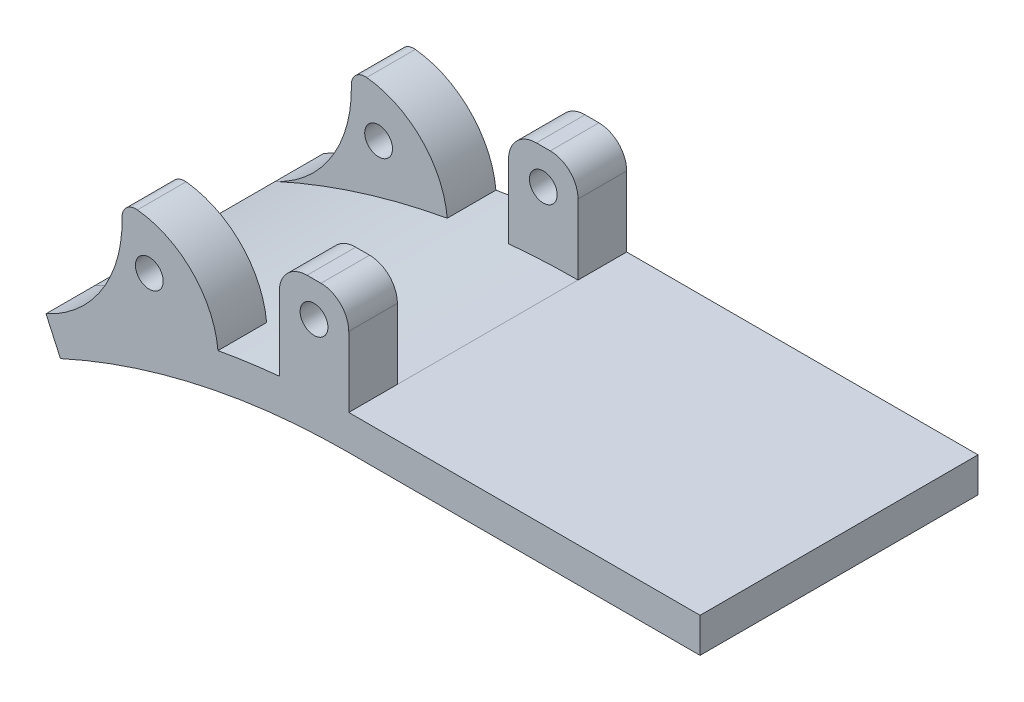
SolidWorks part; units mm, degrees
material "PLA"
ref_plane "Front Plane" through (0, 0, 0) normal (0, 0, 1) x (1, 0, 0)
ref_plane "Top Plane" through (0, 0, 0) normal (0, 1, 0) x (1, 0, 0)
ref_plane "Right Plane" through (0, 0, 0) normal (1, 0, 0) x (0, 0, -1)
sketch "Sketch1" plane through (0, 0, 0) normal (0, 0, 1) x (1, 0, 0)
  line L0 (93.6716, -39.9694) -> (93.6716, -40.9694)
  line L1 (3.6716, -40.9694) -> (3.6716, -39.9694)
  line L2 (3.6716, -39.9694) -> (-32.9868, -39.9694) construction
  line L3 (93.6716, -40.9694) -> (94.0742, -40.9694)
  line L4 (93.6271, -20.4794) -> (94.053, -20.4794)
  line L7 (93.6516, -21.4794) -> (42.6716, -21.4794)
  line L8 (93.6482, -40.9694) -> (93.6716, -40.9694)
  line L9 (93.6271, -20.4794) -> (42.6716, -20.4794)
  line L17 (93.6482, -40.9694) -> (3.6716, -40.9694) construction
  line L19 (93.6716, -39.9694) -> (3.6716, -39.9694) construction
  arc A0 (93.6516, -21.4794) -> (93.6716, -39.9694) centre (94.1163, -30.7239) cw construction
  arc A1 (42.6716, -21.4794) -> (1.5932, -30.4219) centre (42.6716, -120.3004) ccw
  arc A2 (1.5932, -30.4219) -> (3.6716, -39.9694) centre (3.6716, -34.9694) ccw
  arc A3 (93.6271, -20.4794) -> (93.6482, -40.9694) centre (94.1163, -30.7239) cw construction
  arc A4 (1.1775, -29.5124) -> (3.6716, -40.9694) centre (3.6716, -34.9694) ccw
  arc A5 (42.6716, -20.4794) -> (1.1775, -29.5124) centre (42.6716, -120.3004) ccw
  arc A6 (93.6516, -21.4794) -> (93.6716, -39.9694) centre (94.1163, -30.7239) cw construction
  arc A7 (93.6716, -39.9694) -> (93.6516, -21.4794) centre (84.5221, -30.7343) ccw
  arc A8 (94.0742, -40.9694) -> (94.053, -20.4794) centre (84.5221, -30.7343) ccw
  arc A9 (94.3754, -40.6798) -> (94.3539, -20.7675) centre (84.5221, -30.7343) ccw construction
  dimension "D9" = 5
  dimension "D6" = 13
  dimension "D2" = 1
  dimension "D3" = 50.98
  dimension "D4" = 19.49
  dimension "D5" = 90
  dimension "D7" = 1
  dimension "D8" = 39
  dimension "D1" = 1
extrude "Boss-Extrude1" add sketch "Sketch1" along normal blind 38 contours L9 A5 A4 A2 A1 L7 A0 L8 A3 region at (97.6251, -30.7201, 0)
sketch "Sketch2" plane through (0, 0, 0) normal (0, 0, -1) x (-1, 0, 0)
  line L0 (-93.6716, -40.9694) -> (-3.6716, -40.9694)
  line L6 (-93.6716, -40.9694) -> (-93.6716, -39.9694)
  line L7 (-94.0742, -40.9694) -> (-93.6716, -40.9694)
  line L8 (-42.6716, -20.4794) -> (-94.053, -20.4794)
  line L9 (-94.0742, -40.9694) -> (-93.6716, -40.9694)
  line L10 (-3.6716, -39.9694) -> (-3.6716, -40.9694)
  line L12 (-93.6516, -21.4794) -> (-42.6716, -21.4794)
  line L16 (-42.6716, -20.4794) -> (-94.053, -20.4794)
  arc A6 (-93.6516, -21.4794) -> (-93.6716, -39.9694) centre (-84.5221, -30.7343) ccw
  arc A8 (-1.5932, -30.4219) -> (-42.6716, -21.4794) centre (-42.6716, -120.3004) ccw
  arc A9 (-3.6716, -39.9694) -> (-1.5932, -30.4219) centre (-3.6716, -34.9694) ccw
  arc A10 (-3.6716, -40.9694) -> (-1.1775, -29.5124) centre (-3.6716, -34.9694) ccw
  arc A11 (-1.1775, -29.5124) -> (-42.6716, -20.4794) centre (-42.6716, -120.3004) ccw
  arc A12 (-94.053, -20.4794) -> (-94.0742, -40.9694) centre (-84.5221, -30.7343) ccw
  arc A13 (-94.053, -20.4794) -> (-94.0742, -40.9694) centre (-84.5221, -30.7343) ccw
  arc A16 (-3.6716, -40.9694) -> (-1.1775, -29.5124) centre (-3.6716, -34.9694) ccw
  arc A17 (-1.1775, -29.5124) -> (-42.6716, -20.4794) centre (-42.6716, -120.3004) ccw
  dimension "D1" = 0
extrude "Boss-Extrude2" add sketch "Sketch2" along normal blind 1
ref_plane "Plane1" through (0, 0, 19) normal (0, 0, 1) x (1, 0, 0)
mirror "Mirror1" about plane through (0, 0, 19) normal (0, 0, 1) of "Boss-Extrude2"
sketch "Sketch5" plane through (0, -21.4794, 0) normal (0, -1, 0) x (1, 0, 0)
  line L0 (42.6716, 38) -> (42.6716, 0) construction
  line L1 (45.3016, 27.89) -> (45.3016, 10.11) construction
  circle A0 centre (45.3016, 27.89) radius 1.5
  circle A1 centre (45.3016, 10.11) radius 1.5
  circle A2 centre (91.0216, 27.89) radius 1.5
  circle A3 centre (91.0216, 10.11) radius 1.5
  point P6 (42.6716, 19)
  point P7 (45.3016, 19)
  dimension "D3" = 3
  dimension "D1" = 2.63
  dimension "D2" = 17.78
  dimension "D4" = 2
extrude "Boss-Extrude4" add sketch "Sketch5" along normal blind 2
sketch "Sketch6" plane through (0.0001, -40.9694, 0) normal (0, -1, 0) x (1, 0, 0)
  line L0 (3.6715, 38) -> (3.6715, 0) construction
  line L2 (3.6715, 31.5) -> (-0.3285, 31.5)
  line L3 (3.6715, 31.5) -> (3.6715, 6.5)
  line L4 (3.6715, 6.5) -> (-0.3285, 6.5)
  line L5 (-0.3285, 31.5) -> (-0.3285, 6.5)
  point P6 (3.6715, 19)
  point P7 (-0.3285, 19)
  dimension "D1" = 25
  dimension "D2" = 4
extrude "Cut-Extrude1" cut sketch "Sketch6" against normal up to next
ref_plane "Plane2" through (98.5221, 0, 0) normal (1, 0, 0) x (0, 0, -1)
sketch "Sketch7" plane through (98.5221, 0, 0) normal (1, 0, 0) x (0, 0, -1)
  line L1 (-25, -20.4794) -> (-13, -20.4794)
  line L2 (-25, -20.4794) -> (-25, -27.4794)
  line L3 (-25, -27.4794) -> (-13, -27.4794)
  line L4 (-13, -20.4794) -> (-13, -27.4794)
  line L5 (-39, -20.4794) -> (1, -20.4794) construction
  point P7 (-19, -20.4794)
  dimension "D1" = 12
  dimension "D2" = 7
extrude "Cut-Extrude2" cut sketch "Sketch7" against normal up to vertex (4.8705 mm away) up to point (93.6516, -21.4794, 0)
sketch "Sketch8" plane through (93.6516, 0, 0) normal (1, 0, 0) x (0, 0, -1)
  line L0 (-13, -27.4794) -> (-25, -27.4794) construction
  line L1 (-13, -20.4794) -> (-13, -27.4794) construction
  line L2 (-25, -27.4794) -> (-25, -20.4794) construction
  line L3 (-13, -20.4794) -> (-13, -27.4794) construction
  line L4 (-25, -27.4794) -> (-25, -20.4794) construction
  line L5 (-25, -27.4794) -> (-13, -27.4794) construction
  line L6 (-12, -20.4794) -> (-12, -28.4794)
  line L7 (-26, -28.4794) -> (-12, -28.4794)
  line L8 (-26, -28.4794) -> (-26, -20.4794)
  line L9 (-26, -20.4794) -> (-12, -20.4794)
  line L11 (-22.5, -23.1794) -> (-15.5, -23.1794)
  line L12 (-22.5, -23.1794) -> (-22.5, -25.1794)
  line L13 (-22.5, -25.1794) -> (-15.5, -25.1794)
  line L14 (-15.5, -23.1794) -> (-15.5, -25.1794)
  line L15 (-13, -20.4794) -> (1, -20.4794) construction
  point P12 (-19, -23.1794)
  point P13 (-19, -20.4794)
  dimension "D2" = 7
  dimension "D3" = 2
  dimension "D4" = 2.7
  dimension "D1" = 1
extrude "Boss-Extrude5" add sketch "Sketch8" along normal blind 1
sketch "Sketch9" plane through (0, 0, 26) normal (0, 0, 1) x (1, 0, 0)
  line L2 (94.6516, -21.0702) -> (94.6516, -20.4794)
  line L3 (94.6516, -20.4794) -> (94.053, -20.4794)
  line L4 (94.6516, -21.0702) -> (94.6516, -20.4794)
  line L5 (94.6516, -20.4794) -> (94.053, -20.4794)
  arc A1 (94.6516, -21.0702) -> (94.053, -20.4794) centre (84.5221, -30.7343) ccw
  arc A2 (94.6516, -21.0702) -> (94.053, -20.4794) centre (84.5221, -30.7343) ccw
  dimension "D1" = 0
extrude "Cut-Extrude3" cut sketch "Sketch9" against normal up to next
sketch "Sketch10" plane through (94.6516, 0, 0) normal (1, 0, 0) x (0, 0, -1)
  line L0 (-26, -22.586) -> (-26, -28.4794) construction
  line L1 (-26, -28.4794) -> (-12, -28.4794) construction
  line L2 (-12, -28.4794) -> (-12, -22.586) construction
  line L3 (-26, -22.586) -> (-26, -28.4794)
  line L4 (-26, -28.4794) -> (-12, -28.4794)
  line L5 (-12, -28.4794) -> (-12, -22.586)
  line L6 (-25, -22.586) -> (-25, -27.4794)
  line L7 (-25, -27.4794) -> (-13, -27.4794)
  line L8 (-13, -27.4794) -> (-13, -22.586)
  line L9 (-26, -22.586) -> (-25, -22.586)
  line L10 (-12, -22.586) -> (-13, -22.586)
  dimension "D1" = 1
extrude "Boss-Extrude6" add sketch "Sketch10" along normal up to next
fillet "Fillet1" radius 2 1 edges at (94.053, -20.4794, 19)
fillet "Fillet2" radius 1.5 2 edges at (93.6516, -28.4794, 19) (94.6516, -21.0709, 19)
sketch "Sketch11" plane through (0, 0, 39) normal (0, 0, 1) x (1, 0, 0)
  line L1 (94.0742, -40.9694) -> (94.0742, -27.4794)
  line L2 (42.6716, -27.4794) -> (93.2317, -27.4794)
  line L3 (42.6716, -27.4794) -> (94.0742, -27.4794)
  line L4 (94.0742, -40.9694) -> (3.6716, -40.9694) construction
  line L5 (94.0742, -40.9694) -> (3.6716, -40.9694)
  arc A1 (1.1775, -29.5124) -> (3.6716, -40.9694) centre (3.6716, -34.9694) ccw construction
  arc A2 (42.6716, -27.4794) -> (4.0873, -35.8789) centre (42.6716, -120.3004) ccw
  arc A3 (42.6716, -27.4794) -> (-1.1844, -38.4934) centre (42.6716, -120.3004) ccw
  arc A4 (-1.1844, -38.4934) -> (3.6716, -40.9694) centre (3.6716, -34.9694) ccw
  dimension "D1" = 7
extrude "Cut-Extrude4" cut sketch "Sketch11" against normal up to surface (1 mm away) up to face at (47.448, -33.4117, 38)
sketch "Sketch12" plane through (0, 0, 38) normal (0, 0, 1) x (1, 0, 0)
  line L0 (0.6716, -40.1656) -> (0.6716, -38.9694)
  line L1 (3.6716, -40.9694) -> (3.6716, -39.9694)
  line L2 (3.6716, -40.9694) -> (3.6716, -39.9694)
  line L3 (-0.3284, -37.9694) -> (-0.3284, -39.4415) construction
  arc A3 (-0.2899, -38.0201) -> (3.6716, -39.9694) centre (3.6716, -34.9694) ccw
  arc A4 (-0.2899, -38.0201) -> (-1.1844, -38.4934) centre (42.6716, -120.3004) ccw
  arc A5 (-1.1844, -38.4934) -> (3.6716, -40.9694) centre (3.6716, -34.9694) ccw
  arc A6 (0.6716, -38.9694) -> (3.6716, -39.9694) centre (3.6716, -34.9694) ccw
  arc A8 (0.6716, -40.1656) -> (3.6716, -40.9694) centre (3.6716, -34.9694) ccw
  dimension "D2" = 1
  dimension "D1" = 0
extrude "Cut-Extrude5" cut sketch "Sketch12" against normal through all both and the other way through all
sketch "Sketch13" plane through (0, 0, -1) normal (0, 0, -1) x (-1, 0, 0)
  line L0 (-94.0742, -27.4794) -> (-94.0742, -39.5523) construction
  line L1 (-42.6716, -27.4794) -> (-94.0742, -27.4794) construction
  line L2 (-94.0742, -27.4794) -> (-94.0742, -40.9694)
  line L3 (-42.6716, -27.4794) -> (-94.0742, -27.4794)
  line L4 (-94.0742, -40.9694) -> (-3.6716, -40.9694) construction
  line L6 (-3.6716, -40.9694) -> (-3.6716, -39.9694) construction
  line L7 (-3.6716, -40.9694) -> (-3.6716, -39.9694)
  line L8 (-94.0742, -40.9694) -> (-3.6716, -40.9694)
  line L9 (-0.6716, -38.9694) -> (-0.6716, -40.1656) construction
  line L10 (-0.6716, -38.9694) -> (-0.6716, -40.1656)
  arc A0 (0.2899, -38.0201) -> (-42.6716, -27.4794) centre (-42.6716, -120.3004) ccw construction
  arc A1 (1.1844, -38.4934) -> (-42.6716, -27.4794) centre (-42.6716, -120.3004) ccw
  arc A2 (-0.6716, -40.1656) -> (-1.1775, -29.5124) centre (-3.6716, -34.9694) ccw construction
  arc A3 (-3.6716, -39.9694) -> (-0.6716, -38.9694) centre (-3.6716, -34.9694) ccw construction
  arc A4 (-3.6716, -39.9694) -> (-0.6716, -38.9694) centre (-3.6716, -34.9694) ccw
  arc A5 (-0.6716, -40.1656) -> (1.1844, -38.4934) centre (-3.6716, -34.9694) ccw
extrude "Cut-Extrude6" cut sketch "Sketch13" against normal up to surface (1 mm away) up to face at (41.7676, -33.9994, 0)
sketch "Sketch14" plane through (0, 0, 39) normal (0, 0, 1) x (1, 0, 0)
  line L0 (42.6716, -20.4794) -> (93.2317, -20.4794) construction
  line L1 (42.6716, -20.4794) -> (93.2317, -20.4794)
  line L2 (42.6716, -15.4794) -> (93.2317, -15.4794)
  line L3 (93.2317, -15.4794) -> (93.2317, -20.4794)
  line L4 (-0.9009, -24.9648) -> (1.1775, -29.5124)
  arc A0 (42.6716, -20.4794) -> (1.1775, -29.5124) centre (42.6716, -120.3004) ccw construction
  arc A1 (42.6716, -20.4794) -> (1.1775, -29.5124) centre (42.6716, -120.3004) ccw
  arc A2 (42.6716, -15.4794) -> (-0.9009, -24.9648) centre (42.6716, -120.3004) ccw
  dimension "D1" = 5
extrude "Boss-Extrude7" add sketch "Sketch14" against normal through all
sketch "Sketch15" plane through (0, 0, 39) normal (0, 0, 1) x (1, 0, 0)
  line L1 (93.2317, -20.4794) -> (113.7547, -15.9393)
  line L2 (93.2317, -20.4794) -> (42.6716, -20.4794)
  line L3 (93.2317, -20.4794) -> (42.6716, -20.4794)
  line L4 (113.7547, -15.9393) -> (103.4932, -63.6557)
  line L5 (103.4932, -63.6557) -> (-19.8558, -63.6557)
  line L6 (-19.8558, -63.6557) -> (-16.2852, -25.9881)
  line L7 (-16.2852, -25.9881) -> (1.1775, -29.5124)
  arc A2 (42.6716, -20.4794) -> (1.1775, -29.5124) centre (42.6716, -120.3004) ccw
  arc A3 (42.6716, -20.4794) -> (1.1775, -29.5124) centre (42.6716, -120.3004) ccw
  dimension "D1" = 5
extrude "Cut-Extrude7" cut sketch "Sketch15" against normal through all
sketch "Sketch16" plane through (0, 0, -1) normal (0, 0, -1) x (-1, 0, 0)
  arc A0 (0.9009, -24.9648) -> (-42.6716, -15.4794) centre (-42.6716, -120.3004) ccw construction
  arc A1 (0.9009, -24.9648) -> (-23.8475, -17.1835) centre (-42.6716, -120.3004) ccw
  arc A2 (-23.8475, -17.1835) -> (-12.255, -5.4379) centre (-10.8927, -18.3759) cw
  arc A3 (0.9009, -24.9648) -> (-10.0461, -7.4741) centre (8.6924, -7.9172) cw
  circle A4 centre (-13.9663, -12.4794) radius 2
  arc A5 (-10.0461, -7.4741) -> (-12.255, -5.4379) centre (-12.0455, -7.4269) ccw
  point P7 (-14.98, -12.4994)
  point P10 (-13.9663, -12.4794)
  dimension "D1" = 4
  dimension "D2" = 2
extrude "Boss-Extrude8" add sketch "Sketch16" against normal blind 7
sketch "Sketch17" plane through (0, 0, 39) normal (0, 0, 1) x (1, 0, 0)
  circle A0 centre (13.9663, -12.4794) radius 2 construction
  circle A1 centre (13.9663, -12.4794) radius 2
  arc A4 (-0.9009, -24.9648) -> (10.0461, -7.4741) centre (-8.6924, -7.9172) ccw
  arc A5 (23.8475, -17.1835) -> (-0.9009, -24.9648) centre (42.6716, -120.3004) ccw
  arc A6 (23.8475, -17.1835) -> (12.255, -5.4379) centre (10.8927, -18.3759) ccw
  arc A7 (12.255, -5.4379) -> (10.0461, -7.4741) centre (12.0455, -7.4269) ccw
  arc A8 (-0.9009, -24.9648) -> (10.0461, -7.4741) centre (-8.6924, -7.9172) ccw
  arc A9 (23.8475, -17.1835) -> (-0.9009, -24.9648) centre (42.6716, -120.3004) ccw
  arc A10 (23.8475, -17.1835) -> (12.255, -5.4379) centre (10.8927, -18.3759) ccw
  arc A11 (12.255, -5.4379) -> (10.0461, -7.4741) centre (12.0455, -7.4269) ccw
  dimension "D1" = 0
extrude "Boss-Extrude9" add sketch "Sketch17" against normal blind 7
sketch "Sketch18" plane through (0, 0, 39) normal (0, 0, 1) x (1, 0, 0)
  line L2 (42.6716, -15.4794) -> (42.6716, -5.3768)
  line L3 (38.6716, -1.3768) -> (36.6716, -1.3768)
  line L4 (32.6716, -15.9575) -> (32.6716, -5.3768)
  circle A0 centre (37.6716, -6.3768) radius 2
  arc A1 (42.6716, -15.4794) -> (23.8475, -17.1835) centre (42.6716, -120.3004) ccw construction
  arc A2 (42.6716, -15.4794) -> (32.6716, -15.9575) centre (42.6716, -120.3004) ccw
  arc A3 (42.6716, -5.3768) -> (38.6716, -1.3768) centre (38.6716, -5.3768) ccw
  arc A4 (36.6716, -1.3768) -> (32.6716, -5.3768) centre (36.6716, -5.3768) ccw
  point P7 (31.3832, -16.089)
  point P9 (32.184, -16.0054)
  point P11 (0, 0)
  point P12 (37.6716, -1.3768)
  dimension "D1" = 4
  dimension "D2" = 4
  dimension "D3" = 10
  dimension "D4" = 5
extrude "Boss-Extrude10" add sketch "Sketch18" against normal blind 7
sketch "Sketch19" plane through (0, 0, -1) normal (0, 0, -1) x (-1, 0, 0)
  line L3 (-32.6716, -15.9575) -> (-32.6716, -5.3768)
  line L4 (-36.6716, -1.3768) -> (-38.6716, -1.3768)
  line L5 (-42.6716, -5.3768) -> (-42.6716, -15.4794)
  line L6 (-32.6716, -15.9575) -> (-32.6716, -5.3768)
  line L7 (-36.6716, -1.3768) -> (-38.6716, -1.3768)
  line L8 (-42.6716, -5.3768) -> (-42.6716, -15.4794)
  circle A0 centre (-37.6716, -6.3768) radius 2 construction
  circle A1 centre (-37.6716, -6.3768) radius 2
  arc A3 (-32.6716, -15.9575) -> (-42.6716, -15.4794) centre (-42.6716, -120.3004) ccw
  arc A4 (-32.6716, -5.3768) -> (-36.6716, -1.3768) centre (-36.6716, -5.3768) ccw
  arc A5 (-38.6716, -1.3768) -> (-42.6716, -5.3768) centre (-38.6716, -5.3768) ccw
  arc A6 (-32.6716, -15.9575) -> (-42.6716, -15.4794) centre (-42.6716, -120.3004) ccw
  arc A7 (-32.6716, -5.3768) -> (-36.6716, -1.3768) centre (-36.6716, -5.3768) ccw
  arc A8 (-38.6716, -1.3768) -> (-42.6716, -5.3768) centre (-38.6716, -5.3768) ccw
  dimension "D1" = 0
extrude "Boss-Extrude11" add sketch "Sketch19" against normal blind 7
